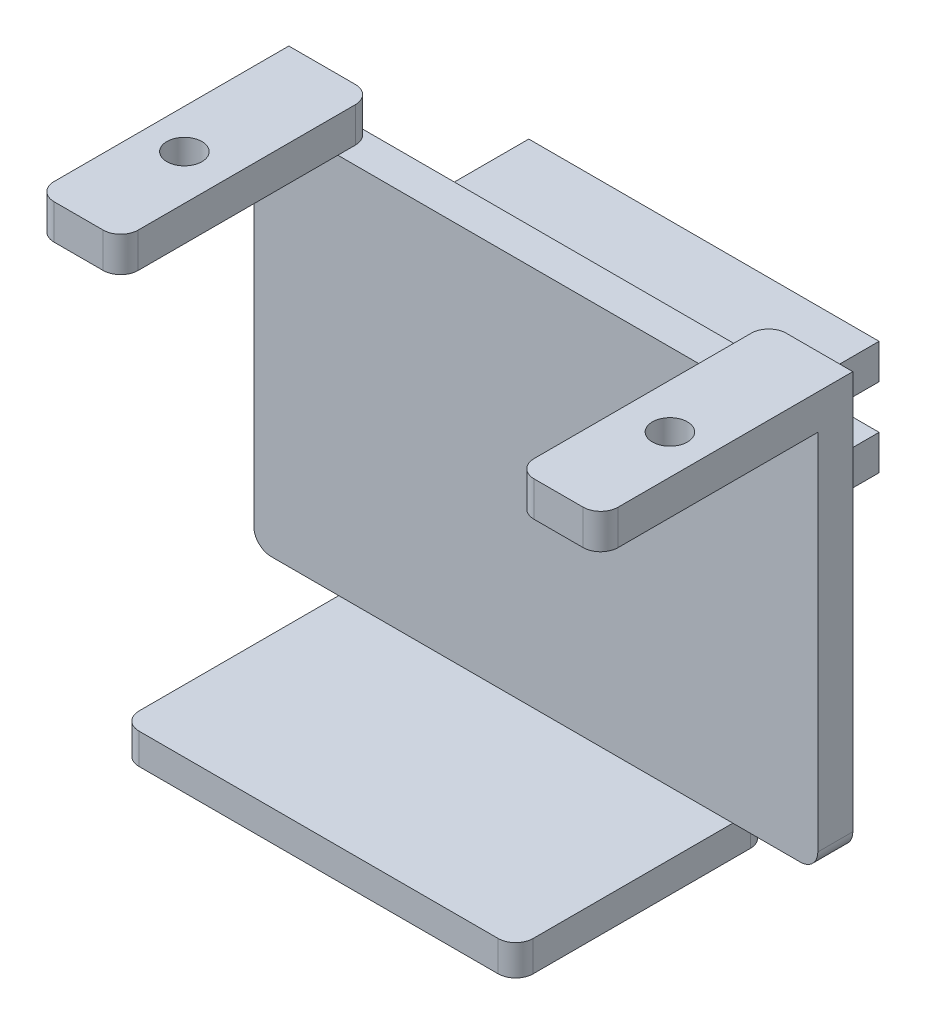
SolidWorks part; units mm, degrees
ref_plane "Front Plane" through (0, 0, 0) normal (0, 0, 1) x (1, 0, 0)
ref_plane "Top Plane" through (0, 0, 0) normal (0, 1, 0) x (1, 0, 0)
ref_plane "Right Plane" through (0, 0, 0) normal (1, 0, 0) x (0, 0, -1)
sketch "Sketch1" plane through (0, 0, 0) normal (0, 0, 1) x (1, 0, 0)
  line L1 (-16.1, 12.75) -> (16.1, 12.75)
  line L2 (-16.1, 12.75) -> (-16.1, -12.75)
  line L3 (-16.1, -12.75) -> (16.1, -12.75)
  line L4 (16.1, 12.75) -> (16.1, -12.75)
  line L5 (-16.1, 12.75) -> (16.1, -12.75) construction
  line L6 (-16.1, -12.75) -> (16.1, 12.75) construction
  point P0 (0, 0)
  dimension "D1" = 32.2
  dimension "D2" = 25.5
extrude "Boss-Extrude1" add sketch "Sketch1" along normal blind 14.4
sketch "Sketch3" plane through (0, 0, 14.4) normal (0, 0, 1) x (1, 0, 0)
  line L0 (-16.1, 12.75) -> (-16.1, -12.75) construction
  line L1 (-16.1, 10.75) -> (16.1, 10.75)
  line L2 (-16.1, 10.75) -> (-16.1, -11)
  line L3 (-16.1, -11) -> (16.1, -11)
  line L4 (16.1, 10.75) -> (16.1, -11)
  line L5 (16.1, -12.75) -> (16.1, 12.75) construction
  line L6 (16.1, 12.75) -> (-16.1, 12.75) construction
  dimension "D1" = 2
  dimension "D2" = 21.75
extrude "Cut-Extrude1" cut sketch "Sketch3" against normal blind 12.4
sketch "Sketch5" plane through (0, 0, 14.4) normal (0, 0, 1) x (1, 0, 0)
  line L0 (16.1, 12.75) -> (-16.1, 12.75) construction
  line L1 (-11.3, 12.75) -> (11.3, 12.75)
  line L2 (-11.3, 12.75) -> (-11.3, 10.75)
  line L3 (-11.3, 10.75) -> (11.3, 10.75)
  line L4 (11.3, 12.75) -> (11.3, 10.75)
  line L5 (16.1, 10.75) -> (-16.1, 10.75) construction
  line L6 (-16.1, 12.75) -> (-16.1, 10.75) construction
  line L7 (16.1, 10.75) -> (16.1, 12.75) construction
  dimension "D1" = 4.8
  dimension "D2" = 4.8
extrude "Cut-Extrude2" cut sketch "Sketch5" against normal blind 14.4 contours L2 L1 L4 L3
fillet "Fillet1" radius 1 1 edges at (-11.3, 11.75, 14.4)
fillet "Fillet2" radius 1 1 edges at (-16.1, 11.75, 14.4)
fillet "Fillet3" radius 1 1 edges at (11.3, 11.75, 14.4)
fillet "Fillet4" radius 1 1 edges at (16.1, 11.75, 14.4)
sketch "Sketch10" plane through (0, 12.75, 0) normal (0, 1, 0) x (1, 0, 0)
  line L0 (-16.1, -13.4) -> (-16.1, 0) construction
  circle A0 centre (-13.86, -8.203) radius 1
  dimension "D1" = 2.24
extrude "Cut-Extrude3" cut sketch "Sketch10" against normal blind 10
mirror "Mirror1" about plane through (0, 0, 0) normal (1, 0, 0) of "Cut-Extrude3"
sketch "Sketch11" plane through (0, 0, 14.4) normal (0, 0, 1) x (1, 0, 0)
  line L0 (-16.1, -12.75) -> (16.1, -12.75) construction
  line L1 (-16.1, -11) -> (-11.25, -11)
  line L2 (-16.1, -11) -> (-16.1, -12.75)
  line L3 (-16.1, -12.75) -> (-11.25, -12.75)
  line L4 (-11.25, -11) -> (-11.25, -12.75)
  dimension "D1" = 4.85
extrude "Cut-Extrude4" cut sketch "Sketch11" against normal blind 20
mirror "Mirror2" about plane through (0, 0, 0) normal (1, 0, 0) of "Cut-Extrude4"
fillet "Fillet5" radius 1 6 edges at (-11.25, -11.875, 0) (-16.1, -11, 1) (16.1, -11, 1) (11.25, -11.875, 0) (11.25, -11.875, 14.4) (-11.25, -11.875, 14.4)
fillet "Fillet6" radius 1 2 edges at (-11.3, 11.75, 0) (11.3, 11.75, 0)
sketch "Sketch12" plane through (0, 0, 0) normal (0, 0, -1) x (-1, 0, 0)
  line L1 (-12.6, 5.5) -> (7.4, 5.5)
  line L2 (-12.6, 5.5) -> (-12.6, 3.5)
  line L3 (-12.6, 3.5) -> (7.4, 3.5)
  line L4 (7.4, 5.5) -> (7.4, 3.5)
  line L6 (12.3, 10.75) -> (-12.3, 10.75) construction
  line L9 (-16.1, -10) -> (-16.1, 12.75) construction
  dimension "D1" = 5.25
  dimension "D2" = 2
  dimension "D3" = 20
  dimension "D4" = 3.5
extrude "Boss-Extrude2" add sketch "Sketch12" along normal blind 5
sketch "Sketch13" plane through (0, 0, 0) normal (0, 0, -1) x (-1, 0, 0)
  line L0 (7.4, 5.5) -> (-12.6, 5.5) construction
  line L1 (-12.6, 10) -> (7.4, 10)
  line L2 (-12.6, 10) -> (-12.6, 8)
  line L3 (-12.6, 8) -> (7.4, 8)
  line L4 (7.4, 10) -> (7.4, 8)
  dimension "D1" = 2.5
extrude "Boss-Extrude3" add sketch "Sketch13" along normal blind 5
